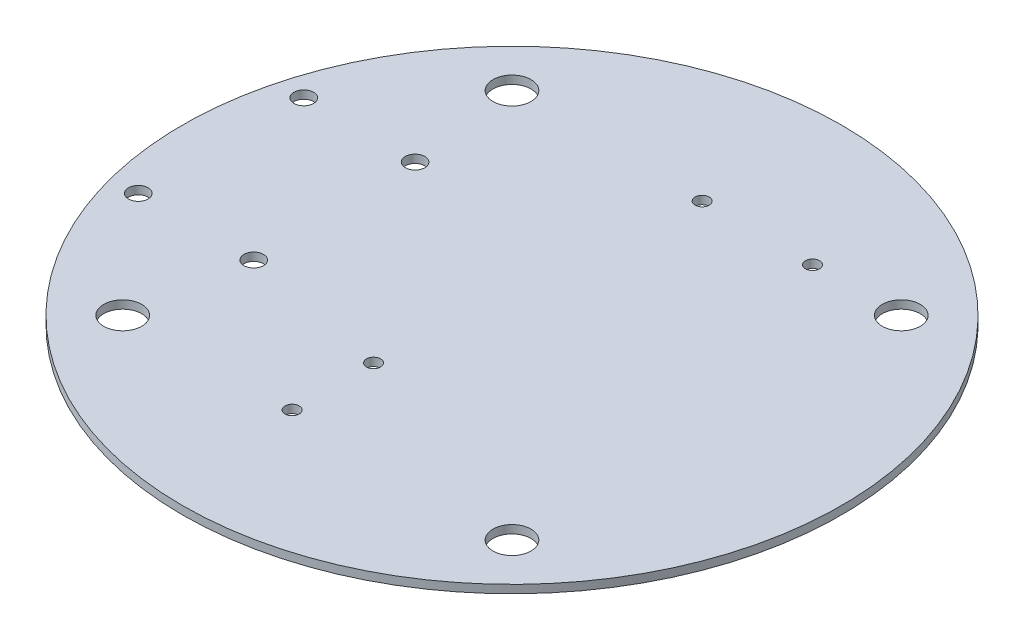
SolidWorks part; units mm, degrees
ref_plane "Front Plane" through (0, 0, 0) normal (0, 0, 1) x (1, 0, 0)
ref_plane "Top Plane" through (0, 0, 0) normal (0, 1, 0) x (1, 0, 0)
ref_plane "Right Plane" through (0, 0, 0) normal (1, 0, 0) x (0, 0, -1)
sketch "Sketch1" plane through (0, 0, 0) normal (0, 1, 0) x (1, 0, 0)
  circle A0 centre (0, 0) radius 60.7
  dimension "PCBdiam" = 121.4
extrude "Boss-Extrude1" add sketch "Sketch1" along normal blind 1.5
hole_wizard "M6 Clearance Hole1" positions "Sketch2" profile "Sketch4" hole size "M6" standard "ANSI Metric" end condition through all
sketch "Sketch2" plane through (0, 1.5, 0) normal (0, 1, 0) x (1, 0, 0)
  line L0 (0, 0) -> (-28.5457, 28.5457) construction
  line L1 (-35.8503, -35.8503) -> (0, 0) construction
  line L3 (0, 0) -> (-73.422, 0) construction
  circle A0 centre (0, 0) radius 60.7 construction
  ellipse E2 centre (-116.4291, -176.9435) end of major axis (-117.7556, -176.0714) minor radius 1.3748
  ellipse E3 centre (-116.4291, -176.9435) end of major axis (-115.1026, -177.8157) minor radius 1.3748
  point P7 (-35.8503, -35.8503)
  dimension "D1" = 0
  dimension "holeRadius" = 50.7
  dimension "D2" = 45
sketch "Sketch4" plane through (-35.8503, 1.5, 35.8503) normal (1, 0, 0) x (0, 0, 1)
  line L0 (0, 0) -> (0, 1.5)
  line L1 (0, 1.5) -> (3.5, 1.5)
  line L2 (3.5, 1.5) -> (3.5, 0)
  line L5 (3.5, 0) -> (0, 0)
  line L11 (0, -6.35) -> (0, 107.95) construction
  dimension "Thru Hole Dia." = 7
  dimension "Thru Hole Depth" = 1.5
pattern_circular "CirPattern1" count 4 over 360 about axis through (0, 1.5, 0) along (0, -1, 0) of "M6 Clearance Hole1"
sketch "Teensy Outline" plane through (0, 1.5, 0) normal (0, 1, 0) x (1, 0, 0)
  line L1 (-27.654, 45.7) -> (-10, 45.7)
  line L2 (-27.654, 45.7) -> (-27.654, -12.72)
  line L3 (-27.654, -12.72) -> (-10, -12.72)
  line L4 (-10, 45.7) -> (-10, -12.72)
  circle A1 centre (0, 0) radius 60.7 construction
  dimension "D1" = 17.654
  dimension "D2" = 58.42
  dimension "D3" = 10
  dimension "D4" = 15
sketch "BMP390 Outline" plane through (0, 1.5, 0) normal (0, 1, 0) x (1, 0, 0)
  line L0 (19.61, 49.7) -> (-3.25, 49.7) construction
  line L2 (22.15, 51.04) -> (-3.25, 51.04)
  line L3 (-3.25, 51.04) -> (-3.25, 33.26)
  line L4 (22.15, 33.26) -> (-3.25, 33.26)
  line L6 (22.15, 51.04) -> (22.15, 33.26)
  line L7 (19.61, 49.7) -> (19.61, 33.26) construction
  line L8 (-27.654, 45.7) -> (-10, 45.7) construction
  line L9 (-10, 45.7) -> (-10, -12.72) construction
  dimension "D1" = 17.78
  dimension "D2" = 25.4
  dimension "D3" = 1.34
  dimension "D4" = 4
  dimension "D5" = 6.75
  dimension "D6" = 5.08
sketch "NEO-6M Outline" plane through (0, 1.5, 0) normal (0, 1, 0) x (1, 0, 0)
  line L0 (-48.84, 17.78) -> (-48.84, 15.24) construction
  line L1 (-56.34, 17.78) -> (-30, 17.78)
  line L2 (-56.34, 17.78) -> (-56.34, -17.78)
  line L3 (-56.34, -17.78) -> (-30, -17.78)
  line L4 (-30, 17.78) -> (-30, -17.78)
  line L5 (-48.84, 15.24) -> (-37.5, 15.24) construction
  line L6 (-37.5, 15.24) -> (-37.5, 17.78) construction
  point P4 (-30, 0)
  point P9 (-43.17, 15.24)
  point P11 (-43.17, 17.78)
  dimension "D1" = 26.34
  dimension "D2" = 35.56
  dimension "D3" = 30
  dimension "D4" = 7.5
  dimension "D5" = 2.54
sketch "Accel, gyro outline" plane through (0, 1.5, 0) normal (0, 1, 0) x (1, 0, 0)
  line L0 (47.32, 26.44) -> (27, 26.44) construction
  line L1 (52.4, 27.78) -> (27, 27.78)
  line L2 (27, 27.78) -> (27, 10)
  line L3 (52.4, 10) -> (27, 10)
  line L4 (52.4, 27.78) -> (52.4, 10)
  line L5 (47.32, 26.44) -> (47.32, 11.34) construction
  line L6 (27, 18.89) -> (52.4, 18.89) construction
  line L7 (47.32, 11.34) -> (27, 11.34) construction
  dimension "D1" = 17.78
  dimension "D2" = 25.4
  dimension "D3" = 1.34
  dimension "D4" = 5.08
  dimension "D5" = 10
  dimension "D6" = 27
sketch "Airspeed sensor outline" plane through (0, 1.5, 0) normal (0, 1, 0) x (1, 0, 0)
  line L0 (-22.654, -23.8503) -> (-29.154, -23.8503) construction
  line L1 (-22.654, -17.8503) -> (-2.654, -17.8503)
  line L2 (-22.654, -17.8503) -> (-22.654, -37.8503)
  line L3 (-22.654, -37.8503) -> (-2.654, -37.8503)
  line L4 (-2.654, -17.8503) -> (-2.654, -37.8503)
  line L5 (-29.154, -23.8503) -> (-29.154, -31.8503) construction
  line L6 (-29.154, -31.8503) -> (-22.654, -31.8503) construction
  line L7 (-27.654, 45.7) -> (-27.654, -12.72) construction
  circle A0 centre (-35.8503, -35.8503) radius 3.5 construction
  point P8 (-29.154, -27.8503)
  point P9 (-22.654, -27.8503)
  dimension "D1" = 20
  dimension "D2" = 20
  dimension "D3" = 6.5
  dimension "D4" = 8
  dimension "D5" = 5
  dimension "D6" = 2
sketch "Xbee outline" plane through (0, 1.5, 0) normal (0, 1, 0) x (1, 0, 0)
  line L0 (9.25, 2.26) -> (9.25, -14.74) construction
  line L1 (4.625, -14.74) -> (13.875, -14.74)
  line L2 (13.875, -14.74) -> (21.5, -8.24)
  line L3 (21.5, -8.24) -> (21.5, 18.26)
  line L4 (21.5, 18.26) -> (-3, 18.26)
  line L5 (-3, -8.24) -> (-3, 18.26)
  line L6 (4.625, -14.74) -> (-3, -8.24)
  line L7 (9.25, -20.0658) -> (9.25, -49.74) construction
  line L8 (22.15, 33.26) -> (-3.25, 33.26) construction
  line L9 (-10, 45.7) -> (-10, -12.72) construction
  line L10 (14.75, -49.74) -> (14.75, -14.74) construction
  line L11 (14.75, -49.74) -> (3.75, -49.74) construction
  line L12 (3.75, -49.74) -> (3.75, -14.74) construction
  line L13 (14.75, -14.74) -> (3.75, -14.74) construction
  point P7 (9.25, 18.26)
  point P11 (9.25, -14.74)
  dimension "D1" = 24.5
  dimension "D2" = 33
  dimension "D3" = 26.5
  dimension "D4" = 9.25
  dimension "D5" = 16
  dimension "D6" = 35
  dimension "D7" = 11
  dimension "D8" = 0
  dimension "D9" = 15
  dimension "D10" = 7
hole_wizard "M2 Clearance Hole1" positions "Sketch20" profile "Sketch19" hole size "M2" standard "ANSI Metric" end condition through all
sketch "Sketch20" plane through (0, 1.5, 0) normal (0, 1, 0) x (1, 0, 0)
  circle A0 centre (-0.71, 35.73) radius 1.2493 construction
  circle A1 centre (19.61, 35.73) radius 1.2493 construction
  circle A2 centre (-5.154, -20.3503) radius 1.25 construction
  circle A3 centre (-5.154, -20.3503) radius 1.25 construction
  circle A4 centre (-5.154, -35.3503) radius 1.25 construction
  circle A5 centre (-5.154, -35.3503) radius 1.25 construction
  point P1 (-0.71, 35.73)
  point P7 (19.61, 35.73)
  point P13 (-5.154, -20.3503)
  point P16 (-5.154, -35.3503)
sketch "Sketch19" plane through (-0.71, 1.5, -35.73) normal (1, 0, 0) x (0, 0, 1)
  line L0 (0, 0) -> (0, 1.5)
  line L1 (0, 1.5) -> (1.3, 1.5)
  line L2 (1.3, 1.5) -> (1.3, 0)
  line L5 (1.3, 0) -> (0, 0)
  line L11 (0, -6.35) -> (0, 107.95) construction
  dimension "Thru Hole Dia." = 2.6
  dimension "Thru Hole Depth" = 1.5
hole_wizard "M3 Clearance Hole2" positions "Sketch21" profile "Sketch22" hole size "M3" standard "ANSI Metric" end condition through all
sketch "Sketch21" plane through (0, 1.5, 0) normal (0, 1, 0) x (1, 0, 0)
  point P0 (-53.8645, 15.5117)
  point P3 (-53.8645, -14.9683)
  point P6 (-32.6045, -14.9683)
  point P9 (-33.3665, 15.5117)
sketch "Sketch22" plane through (-53.8645, 1.5, -15.5117) normal (1, 0, 0) x (0, 0, 1)
  line L0 (0, 0) -> (0, 1.5)
  line L1 (0, 1.5) -> (1.8, 1.5)
  line L2 (1.8, 1.5) -> (1.8, 0)
  line L5 (1.8, 0) -> (0, 0)
  line L11 (0, -6.35) -> (0, 107.95) construction
  dimension "Thru Hole Dia." = 3.6
  dimension "Thru Hole Depth" = 1.5
